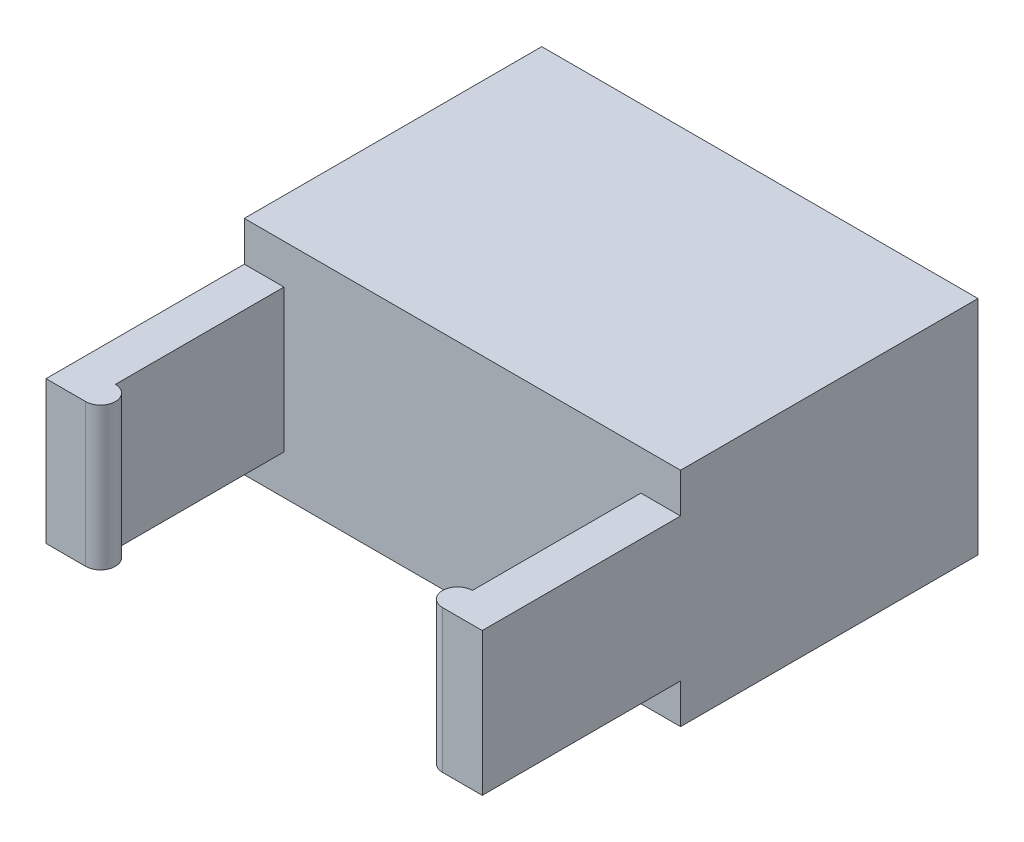
SolidWorks part; units mm, degrees
ref_plane "Front Plane" through (0, 0, 0) normal (0, 0, 1) x (1, 0, 0)
ref_plane "Top Plane" through (0, 0, 0) normal (0, 1, 0) x (1, 0, 0)
ref_plane "Right Plane" through (0, 0, 0) normal (1, 0, 0) x (0, 0, -1)
sketch "Sketch1" plane through (0, 0, 0) normal (0, 0, 1) x (1, 0, 0)
  line L1 (-9, 3.6) -> (9, 3.6)
  line L2 (-9, 3.6) -> (-9, -3.6)
  line L3 (-9, -3.6) -> (9, -3.6)
  line L4 (9, 3.6) -> (9, -3.6)
  line L5 (-9, 3.6) -> (9, -3.6) construction
  line L6 (-9, -3.6) -> (9, 3.6) construction
  line L11 (-5.6882, -3.6) -> (5.6882, 3.6) construction
  line L12 (-5.6882, 3.6) -> (5.6882, -3.6) construction
  line L13 (9, 3.6) -> (11, 3.6)
  line L14 (9, 3.6) -> (9, -3.6)
  line L15 (9, -3.6) -> (11, -3.6)
  line L16 (11, 3.6) -> (11, -3.6)
  line L17 (-9, 3.6) -> (-11, 3.6)
  line L18 (-9, 3.6) -> (-9, -3.6)
  line L19 (-9, -3.6) -> (-11, -3.6)
  line L20 (-11, 3.6) -> (-11, -3.6)
  line L21 (-11, 3.6) -> (11, 3.6)
  line L22 (-11, 3.6) -> (-11, 5.6)
  line L23 (-11, 5.6) -> (11, 5.6)
  line L24 (11, 3.6) -> (11, 5.6)
  line L25 (-11, -3.6) -> (11, -3.6)
  line L26 (-11, -3.6) -> (-11, -5.6)
  line L27 (-11, -5.6) -> (11, -5.6)
  line L28 (11, -3.6) -> (11, -5.6)
  point P0 (0, 0)
  point P6 (0, 0)
  dimension "D1" = 18
  dimension "D2" = 7.2
  dimension "D3" = 2
  dimension "D4" = 2
  dimension "D5" = 2
extrude "Boss-Extrude3" add sketch "Sketch1" along normal blind 15 contours L13 L24 L23 L22 L17 L1 | L17 L20 L19 L2 | L4 L1 L2 L3 | L28 L15 L3 L19 L26 L27 | L16 L13 L4 L15 region at (0, 4.6, 0) region at (0, 0, 0) region at (-10, 0, 0) region at (10, 0, 0) region at (0, -4.6, 0)
extrude "Boss-Extrude4" add sketch "Sketch1<4>" along normal blind 8.5 from surface contours L17 L20 L19 L2 | L16 L13 L4 L15 region at (-10, 0, 0) region at (10, 0, 0) starting at face at (0, 0, 15)
sketch "Sketch1<4>" plane through (0, 0, 0) normal (0, 0, 1) x (1, 0, 0) same geometry as "Sketch1"
sketch "Sketch3" plane through (0, 0, 0) normal (0, 1, 0) x (1, 0, 0)
  line L1 (-9, -23.5) -> (-9, -25) construction
  line L2 (-11, -23.5) -> (-9, -23.5)
  line L3 (-11, -23.5) -> (-11, -25)
  line L4 (-11, -25) -> (-9, -25)
  line L5 (-9, -23.5) -> (-9, -25)
  arc A0 (-9, -25) -> (-9, -23.5) centre (-9, -24.25) ccw
  dimension "D1" = 1.5
extrude "Boss-Extrude5" add sketch "Sketch3" along normal up to surface (3.6 mm away) from surface contours L5 L2 L3 L4 | L5 A0 region at (-10, 0, 24.25) region at (-8.6817, 0, 24.25) up to face at (-10, 3.6, 19.25) starting at face at (-10, -3.6, 19.25)
mirror "Mirror1" about plane through (0, 0, 0) normal (1, 0, 0) of "Boss-Extrude5"
